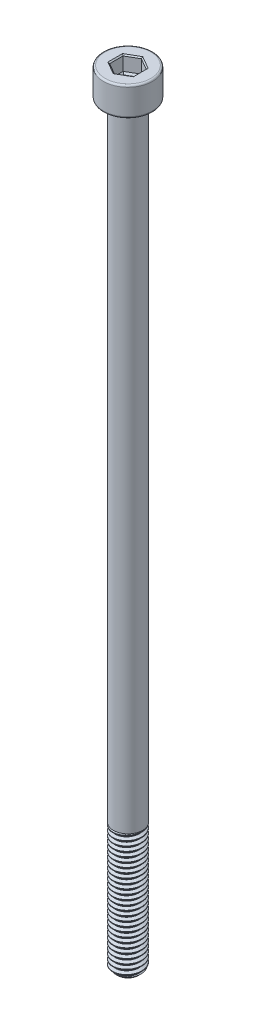
SolidWorks part; units mm, degrees
material "AISI Type A2 Tool Steel"
ref_plane "Front Plane" through (0, 0, 0) normal (0, 0, 1) x (1, 0, 0)
ref_plane "Top Plane" through (0, 0, 0) normal (0, 1, 0) x (1, 0, 0)
ref_plane "Right Plane" through (0, 0, 0) normal (1, 0, 0) x (0, 0, -1)
sketch "Sketch1" plane through (0, 0, 0) normal (0, 1, 0) x (1, 0, 0)
  circle A0 centre (0, 0) radius 2.5
  dimension "D1" = 5
extrude "Boss-Extrude1" add sketch "Sketch1" along normal blind 22
thread "Thread1" pitch 0.8 start angle 0, offset 1, length 0, pitch 0.8, diameter 5
ref_plane "Plane1" through (-2.5, 23, 0) normal (0, 0, 1) x (-1, 0, 0)
sketch "Thread Profile1" plane through (-2.5, 23, 0) normal (0, 0, 1) x (-1, 0, 0)
  line L0 (0, 0) -> (0, 0.8) construction
  line L11 (0, 0) -> (0, 0.7)
  line L12 (0, 0.7) -> (-0.433, 0.45)
  line L13 (-0.433, 0.45) -> (-0.433, 0.25)
  line L15 (-0.433, 0.25) -> (0, 0)
  line L17 (-0.433, 0.35) -> (0, 0.35) construction
  point P2 (0, 0)
  dimension "Pitch" = 0.8
  dimension "Profile_Angle" = 60
  dimension "Profile_Land" = 0.2
  dimension "Profile_Height" = 0.433
sketch "Sketch2" plane through (0, 22, 0) normal (0, 1, 0) x (1, 0, 0)
  circle A0 centre (0, 0) radius 2.5
  dimension "D1" = 5
extrude "Boss-Extrude2" add sketch "Sketch2" along normal blind 108
sketch "Sketch3" plane through (0, 130, 0) normal (0, 1, 0) x (1, 0, 0)
  circle A0 centre (0, 0) radius 4.25
  dimension "D1" = 8.5
extrude "Boss-Extrude3" add sketch "Sketch3" along normal blind 5
fillet "Fillet1" radius 0.3 2 edges at (0, 130, 4.25) (0, 135, 4.25)
sketch "Sketch4" plane through (0, 0, 0) normal (0, 0, 1) x (1, 0, 0)
  line L0 (0, 0) -> (0, 0.4416) construction
  line L1 (0, 0) -> (2.51, 0) construction
  line L2 (2.51, 0) -> (2.51, 0.7)
  line L3 (2.51, 0.7) -> (1.81, 0)
  line L4 (1.81, 0) -> (2.51, 0)
  dimension "D1" = 0.7
  dimension "D2" = 45
  dimension "D3" = 2.51
revolve "Cut-Revolve1" cut sketch "Sketch4" angle 360 about L0
sketch "Sketch5" plane through (0, 135, 0) normal (0, 1, 0) x (1, 0, 0)
  line L1 (0, 2.3094) -> (-2, 1.1547)
  line L2 (-2, 1.1547) -> (-2, -1.1547)
  line L3 (-2, -1.1547) -> (0, -2.3094)
  line L4 (0, -2.3094) -> (2, -1.1547)
  line L5 (2, -1.1547) -> (2, 1.1547)
  line L6 (2, 1.1547) -> (0, 2.3094)
  circle A0 centre (0, 0) radius 2 construction
  dimension "D1" = 4
extrude "Cut-Extrude1" cut sketch "Sketch5" against normal blind 2.5
chamfer "Chamfer1" distance 0.2 angle 45 6 edges at (-1, 135, 1.7321) (1, 135, 1.7321) (2, 135, 0) (1, 135, -1.7321) (-1, 135, -1.7321) (-2, 135, 0)
sketch "Sketch6" plane through (0, 132.5, 0) normal (0, 1, 0) x (1, 0, 0)
  line L1 (0, 2.3094) -> (-2, 1.1547)
  line L2 (-2, 1.1547) -> (-2, -1.1547)
  line L3 (-2, -1.1547) -> (0, -2.3094)
  line L4 (0, -2.3094) -> (2, -1.1547)
  line L5 (2, -1.1547) -> (2, 1.1547)
  line L6 (2, 1.1547) -> (0, 2.3094)
  circle A0 centre (0, 0) radius 2 construction
extrude "Cut-Extrude2" cut sketch "Sketch6" against normal blind 0.3 draft 45
